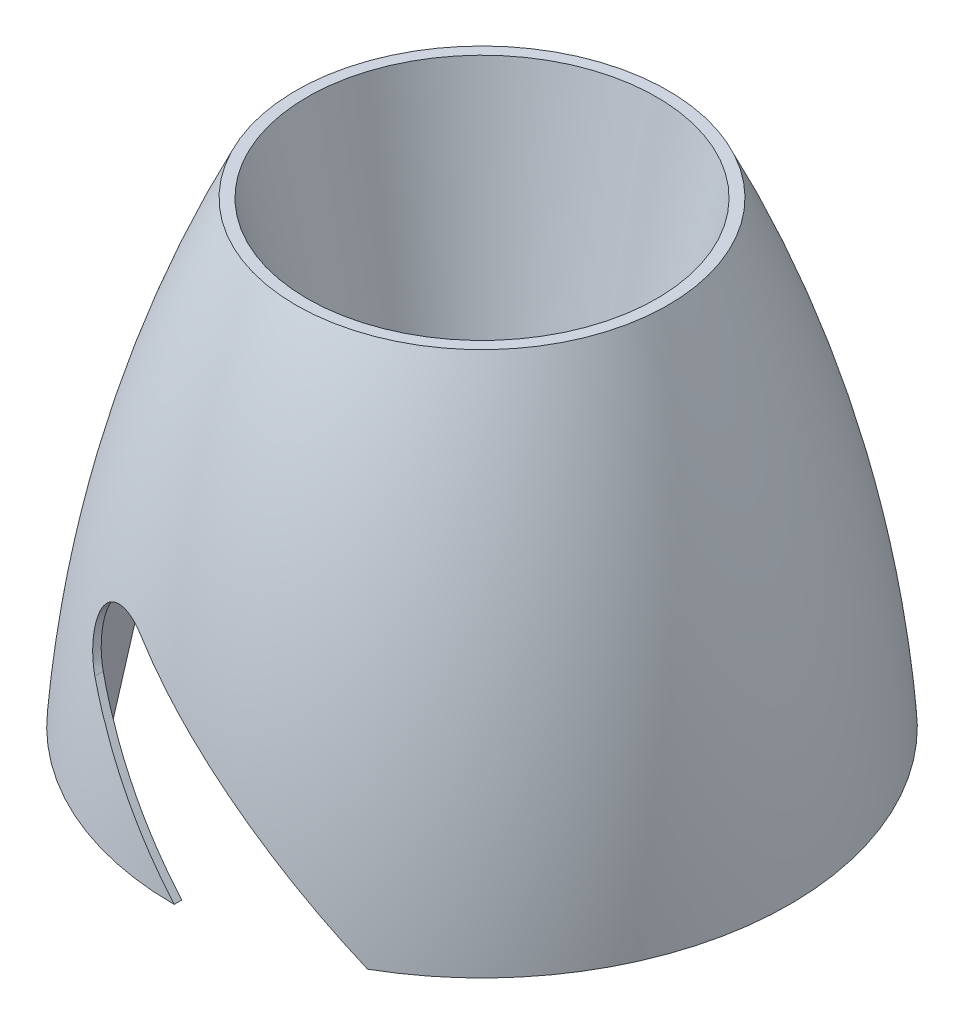
SolidWorks part; units mm, degrees
ref_plane "정면" through (0, 0, 0) normal (0, 0, 1) x (1, 0, 0)
ref_plane "윗면" through (0, 0, 0) normal (0, 1, 0) x (1, 0, 0)
ref_plane "우측면" through (0, 0, 0) normal (1, 0, 0) x (0, 0, -1)
sketch "스케치1" plane through (0, 0, 0) normal (0, 0, 1) x (1, 0, 0)
  line L0 (0, 61) -> (-24.7689, 61)
  line L1 (0, 0) -> (-41, 0)
  line L2 (0, 0) -> (0, 61)
  line L3 (0, 85.2102) -> (0, -22.101) construction
  arc A0 (-41, 0) -> (-24.7689, 61) centre (128.5433, -12.4532) cw
  dimension "D5" = 170
  dimension "D4" = 24.7689
  dimension "D1" = 41
  dimension "D2" = 61
  dimension "D3" = 12.4532
revolve "회전1" add sketch "스케치1" angle 360 about L3
sketch "스케치2" plane through (0, 61, 0) normal (0, 1, 0) x (1, 0, 0)
  circle A2 centre (0, 0) radius 23.2689
  circle A3 centre (0, 0) radius 23.2689
  dimension "D1" = 1.5
extrude "돌출1" cut sketch "스케치2" against normal blind 33 draft 12
shell "쉘1" thickness 1 removed face at (0, 0, 41)
sketch "스케치5" plane through (0, 27, 0) normal (0, -1, 0) x (1, 0, 0)
  circle A1 centre (0, 0) radius 17.0643
  circle A2 centre (0, 0) radius 17.0643
  dimension "D1" = 0
extrude "돌출4" add sketch "스케치5" along normal blind 1 draft 12
sketch "스케치3" plane through (0, 0, 0) normal (0, 1, 0) x (1, 0, 0)
  circle A0 centre (0, 0) radius 8
  dimension "D1" = 16
extrude "돌출2" cut sketch "스케치3" along normal blind 40
sketch "스케치4" plane through (0, 0, 0) normal (0, 0, 1) x (1, 0, 0)
  line L0 (0, 0) -> (-15.8076, 15.8076)
  line L2 (-41, 0) -> (41, 0) construction
  line L3 (0, 0) -> (14.1421, -14.1421)
  line L4 (14.1421, -14.1421) -> (24.0416, -4.2426)
  line L5 (-24.9651, 25) -> (7.7284, 25) construction
  arc A0 (-9.2381, 24.2378) -> (-15.8076, 15.8076) centre (-12, 19.6152) ccw
  arc A1 (-9.2381, 24.2378) -> (24.0416, -4.2426) centre (-75.9158, -87.3601) cw
  dimension "D2" = 12
  dimension "D1" = 130
  dimension "D3" = 45
  dimension "D4" = 90
  dimension "D6" = 25
  dimension "D7" = 14
extrude "돌출3" cut sketch "스케치4" along normal blind 50 from surface starting at plane "정면"
sketch "스케치6" plane through (0, 0, 0) normal (0, 0, 1) x (1, 0, 0)
  line L0 (0, 0) -> (0, 66.5158) construction
pattern_circular "원형 패턴3" count 2 every 180 about axis through (0, 0, 0) along (0, 1, 0) of "돌출3"
sketch "스케치7" plane through (0, 0, 0) normal (0, 0, 1) x (1, 0, 0)
  line L0 (-33, 24) -> (-37.3394, 2)
  line L1 (0, 0) -> (0, 66.5158) construction
  line L2 (-23.5896, 60.104) -> (-16.3627, 26.104)
  line L3 (-23.5675, 60) -> (-16.4469, 26.5)
  line L4 (-15.4342, 24) -> (-33, 24)
  line L5 (-23.5675, 60) -> (-24.6911, 60)
  line L6 (-16.8518, 26) -> (16.8518, 26) construction
  line L7 (-41, 2) -> (0, 2)
  line L8 (-40.3394, 2) -> (-37.3394, 2)
  line L9 (-24.1379, 60) -> (24.1379, 60) construction
  line L10 (-8, 26.5) -> (-8, 24)
  line L11 (-16.8518, 26.5) -> (16.8518, 26.5)
  line L12 (-16.4469, 26.5) -> (-8, 26.5)
  line L13 (-8, 24) -> (-15.4342, 24)
  arc A2 (-24.5896, 60.2144) -> (-40.4959, 0.0368) centre (128.5433, -12.4532) ccw
  arc A3 (-24.6911, 60) -> (-40.3394, 2) centre (128.5433, -12.4532) ccw
  dimension "D5" = 2
  dimension "D6" = 0.5
  dimension "D3" = 3
  dimension "D7" = 33
  dimension "D8" = 8
  dimension "D1" = 0.5
  dimension "D2" = 0.5
  dimension "D4" = 2
extrude "돌출5" add sketch "스케치7" along normal mid plane 1.5
pattern_circular "원형 패턴4" count 6 every 60 about axis through (0, 0, 0) along (0, 1, 0) of "돌출5"
sketch "스케치8" plane through (0, 26, 0) normal (0, -1, 0) x (1, 0, 0)
  circle A0 centre (0, 0) radius 8
  circle A1 centre (0, 0) radius 10.5
  dimension "D1" = 21
  dimension "D2" = 16
extrude "돌출6" add sketch "스케치8" along normal blind 2
